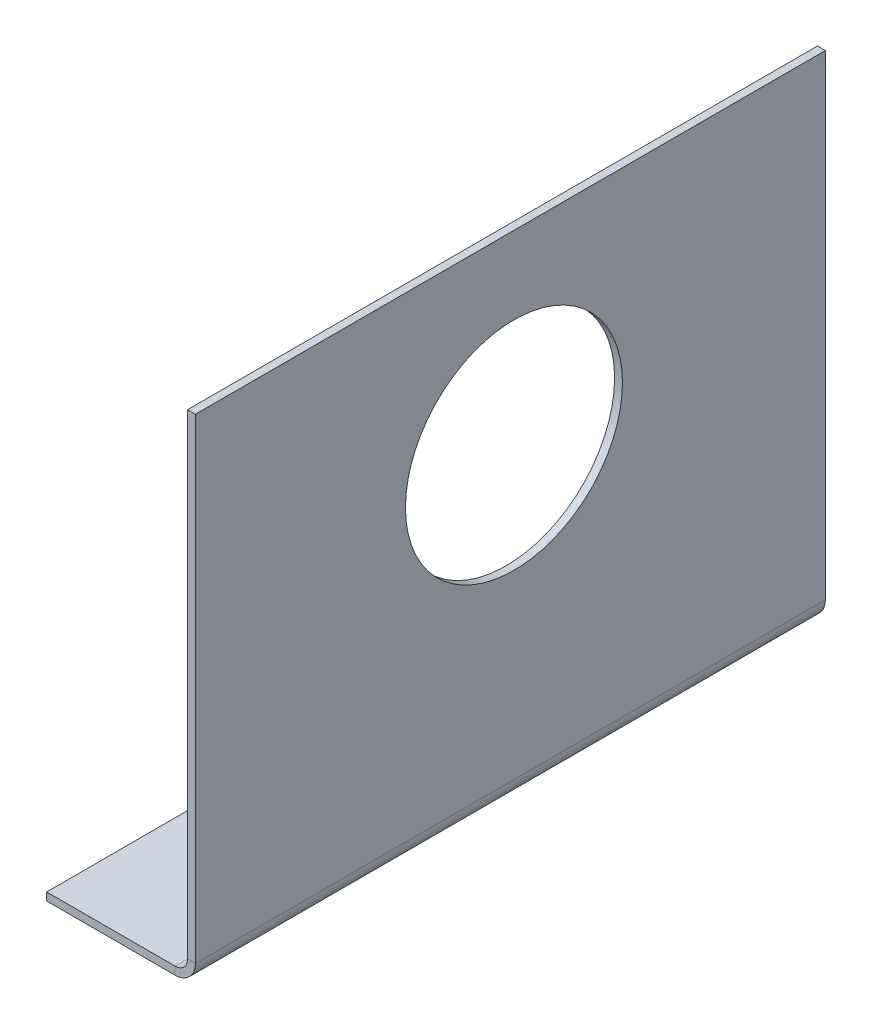
SolidWorks part; units mm, degrees
note: The reader was unsure of these and kept them because the rebuilt part matched: flange length of "Edge-Flange1".
ref_plane "Front Plane" through (0, 0, 0) normal (0, 0, 1) x (1, 0, 0)
ref_plane "Top Plane" through (0, 0, 0) normal (0, 1, 0) x (1, 0, 0)
ref_plane "Right Plane" through (0, 0, 0) normal (1, 0, 0) x (0, 0, -1)
sketch "Sketch1" plane through (0, 0, 0) normal (1, 0, 0) x (0, 0, -1)
  line L1 (-25.4, -20) -> (25.4, -20)
  line L2 (-25.4, -20) -> (-25.4, 20)
  line L3 (-25.4, 20) -> (25.4, 20)
  line L4 (25.4, -20) -> (25.4, 20)
  line L5 (-25.4, -20) -> (25.4, 20) construction
  line L6 (-25.4, 20) -> (25.4, -20) construction
  point P0 (0, 0)
  dimension "D1" = 40
  dimension "D2" = 50.8
base flange "Base-Flange1" sketch "Sketch1" thickness 0.635 reverse thickness direction no parameters "D1"=1
edge flange "Edge-Flange1" sketch "Sketch8" flange angle 90 flange length 12 flange position material inside bend radius 1 thickness 0.635 relief rectangular parameters "D6"=10
sketch "Sketch8" plane through (-0.635, -20, 0) normal (0, -1, 0) x (0, 0, 1)
  line L2 (-25.4, 0) -> (-25.4, 11.365)
  line L3 (-25.4, 11.365) -> (25.4, 11.365)
  line L4 (25.4, 11.365) -> (25.4, 0)
  line L7 (25.4, 0) -> (-25.4, 0) construction
  line L8 (25.4, 0) -> (-25.4, 0)
bend "EdgeBend1" bend radius 1 bend angle 90 parameters "D5"=1
sketch "Sketch9" plane through (0, 0, 0) normal (1, 0, 0) x (0, 0, -1)
  circle A0 centre (0.2879, 5) radius 8.75
  dimension "D2" = 17.5
  dimension "D1" = 5
extrude "Cut-Extrude1" cut sketch "Sketch9" against normal through all normal cut yes
sketch "Sketch10" plane through (0, -19.365, 0) normal (0, 1, 0) x (1, 0, 0)
  line L0 (-6.8175, 25.4) -> (-6.8175, -25.4) construction
  line L1 (-12, 25.4) -> (-1.635, 25.4) construction
  line L2 (-1.635, -25.4) -> (-12, -25.4) construction
  line L3 (-6.8175, -9.5) -> (-6.8175, -14.5) construction
  line L4 (-4.1675, -9.5) -> (-4.1675, -14.5)
  line L5 (-9.4675, -9.5) -> (-9.4675, -14.5)
  circle A0 centre (-6.8175, 12) radius 2.65
  arc A1 (-4.1675, -9.5) -> (-9.4675, -9.5) centre (-6.8175, -9.5) ccw
  arc A2 (-9.4675, -14.5) -> (-4.1675, -14.5) centre (-6.8175, -14.5) ccw
  point P10 (-6.8175, -12)
  dimension "D3" = 5.3
  dimension "D1" = 12
  dimension "D2" = 12
  dimension "D4" = 5.3
  dimension "D5" = 5
extrude "Cut-Extrude2" cut sketch "Sketch10" against normal through all normal cut yes
sketch "Bend-Lines1" [suppressed] plane through (0, 0, 0) normal (0, 1, 0) x (1, 0, 0)
sketch "Bounding-Box1" [suppressed] plane through (0, 0, 0) normal (0, 1, 0) x (1, 0, 0)
sheet metal parameters "Sheet-Metal1" thickness 0.635 parameters "D1"=1
flat pattern "Flat-Pattern1" [suppressed]
sketch "Bend-Lines2" plane through (0, 0, 0) normal (0, 1, 0) x (1, 0, 0)
sketch3d "Bounding-Box2" [suppressed]
  line L0 (-25, -10, 0) -> (25, -10, 0) construction
  line L1 (-25, 10, 0) -> (25, 10, 0) construction
  line L2 (-25, -10, 0) -> (-25, 10, 0) construction
  line L3 (25, -10, 0) -> (25, 10, 0) construction
sheet metal parameters "Sheet-Metal2" thickness 0.635 parameters "D1"=1
flat pattern "Flat-Pattern1"
sketch "Bend-Lines2" plane through (0, 0, 0) normal (1, 0, 0) x (0, 0, -1)
  line L0 (-25.4, -19.3998) -> (25.4, -19.3998) construction
  line L1 (-25.4, -19.3998) -> (25.4, -19.3998) construction
sketch3d "Bounding-Box2" [suppressed]
  line L0 (25.4, -30.7995, 0) -> (-25.4, -30.7995, 0) construction
  line L1 (25.4, 20, 0) -> (-25.4, 20, 0) construction
  line L2 (25.4, -30.7995, 0) -> (25.4, 20, 0) construction
  line L3 (-25.4, -30.7995, 0) -> (-25.4, 20, 0) construction
bend of the flat pattern "Flatten-<EdgeBend1>1"
sheet metal parameters "Sheet-Metal3" thickness 0.635 parameters "D1"=1
flat pattern "Flat-Pattern1"
sketch "Bend-Lines2" plane through (0, 0, 0) normal (1, 0, 0) x (0, 0, -1)
  line L0 (-25.4, -19.3998) -> (25.4, -19.3998) construction
  line L1 (-25.4, -19.3998) -> (25.4, -19.3998) construction
sketch3d "Bounding-Box2" [suppressed]
  line L0 (25.4, -30.7995, 0) -> (-25.4, -30.7995, 0) construction
  line L1 (25.4, 20, 0) -> (-25.4, 20, 0) construction
  line L2 (25.4, -30.7995, 0) -> (25.4, 20, 0) construction
  line L3 (-25.4, -30.7995, 0) -> (-25.4, 20, 0) construction
bend of the flat pattern "Flatten-<EdgeBend1>1"
sheet metal parameters "Sheet-Metal4" thickness 0.635 parameters "D1"=1
flat pattern "Flat-Pattern1"
sketch "Bend-Lines2" plane through (0, 0, 0) normal (1, 0, 0) x (0, 0, -1)
  line L0 (-25.4, -19.3998) -> (25.4, -19.3998) construction
  line L1 (-25.4, -19.3998) -> (25.4, -19.3998) construction
sketch3d "Bounding-Box2" [suppressed]
  line L0 (25.4, -30.7995, 0) -> (-25.4, -30.7995, 0) construction
  line L1 (25.4, 20, 0) -> (-25.4, 20, 0) construction
  line L2 (25.4, -30.7995, 0) -> (25.4, 20, 0) construction
  line L3 (-25.4, -30.7995, 0) -> (-25.4, 20, 0) construction
bend of the flat pattern "Flatten-<EdgeBend1>1"
